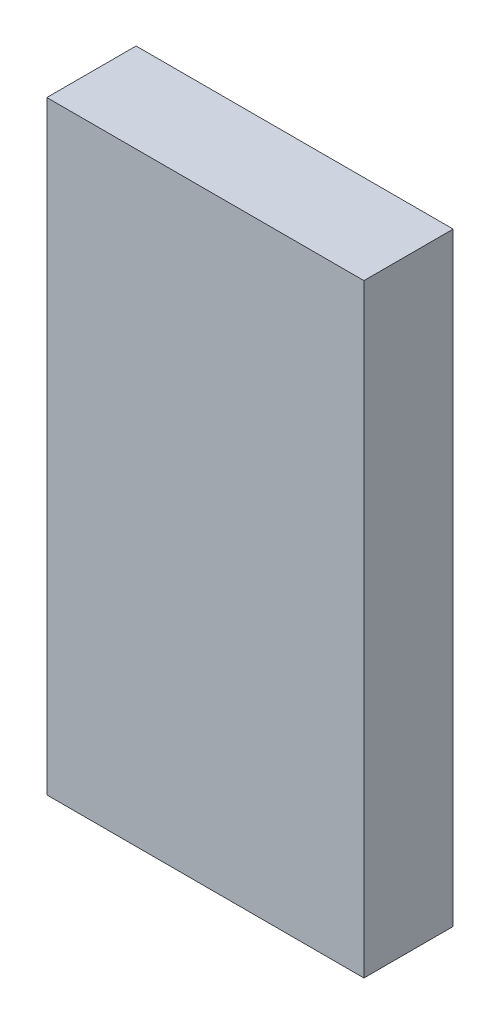
SolidWorks part; units mm, degrees
ref_plane "Plan de face" through (0, 0, 0) normal (0, 0, 1) x (1, 0, 0)
ref_plane "Plan de dessus" through (0, 0, 0) normal (0, 1, 0) x (1, 0, 0)
ref_plane "Plan de droite" through (0, 0, 0) normal (1, 0, 0) x (0, 0, -1)
sketch "Esquisse1" plane through (0, 0, 0) normal (0, 0, 1) x (1, 0, 0)
  line L1 (0, 0) -> (53.3, 0)
  line L2 (0, 0) -> (0, 101.52)
  line L3 (0, 101.52) -> (53.3, 101.52)
  line L4 (53.3, 0) -> (53.3, 101.52)
  dimension "D1" = 53.3
  dimension "D2" = 101.52
extrude "Boss.-Extru.1" add sketch "Esquisse1" along normal blind 15
